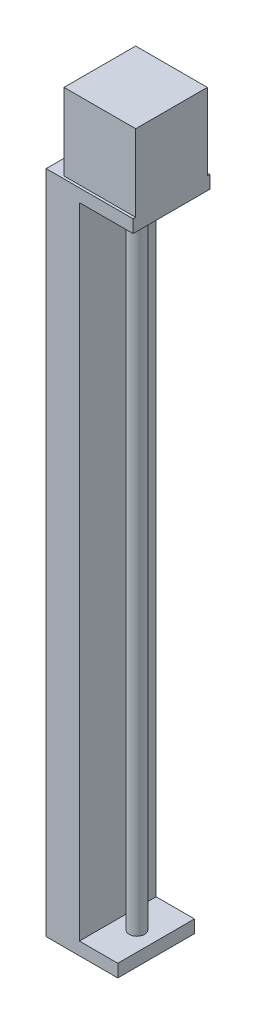
SolidWorks part; units mm, degrees
ref_plane "Front Plane" through (0, 0, 0) normal (0, 0, 1) x (1, 0, 0)
ref_plane "Top Plane" through (0, 0, 0) normal (0, 1, 0) x (1, 0, 0)
ref_plane "Right Plane" through (0, 0, 0) normal (1, 0, 0) x (0, 0, -1)
sketch "Sketch1" plane through (0, 0, 0) normal (0, 0, 1) x (1, 0, 0)
  line L0 (-11, 160) -> (-11, 130)
  line L1 (17, -125) -> (-17, -125)
  line L2 (17, -125) -> (17, 125)
  line L3 (17, 125) -> (-17, 125)
  line L4 (-17, -125) -> (-17, 125)
  line L5 (17, -125) -> (-17, 125) construction
  line L6 (17, 125) -> (-17, -125) construction
  line L7 (-17, -125) -> (11, -125)
  line L8 (-17, -125) -> (-17, -130)
  line L9 (-17, -130) -> (11, -130)
  line L10 (11, -125) -> (11, -130)
  line L11 (-17, 125) -> (17, 125)
  line L12 (-17, 125) -> (-17, 130)
  line L13 (-17, 130) -> (17, 130)
  line L14 (17, 125) -> (17, 130)
  line L15 (-17, 130) -> (17, 130)
  line L17 (-11, 160) -> (17, 160)
  line L18 (17, 130) -> (17, 160)
  line L19 (-4, 125) -> (-4, -125)
  point P0 (0, 0)
  dimension "D1" = 250
  dimension "D2" = 5
  dimension "D3" = 5
  dimension "D4" = 30
  dimension "D5" = 28
  dimension "D6" = 34
  dimension "D7" = 13
  dimension "D8" = 28
extrude "Boss-Extrude1" add sketch "Sketch1" along normal mid plane 30 contours L3 L14 L13 L12 L11 | L19 L11 L4 L7 | L10 L1 L7 L8 L9 region at (0, 127.5, 0) region at (-10.5, 0, 0) region at (-3, -127.5, 0)
extrude "Boss-Extrude2" add sketch "Sketch1<3>" along normal mid plane 28 contours L13 L18 L17 L0 region at (3, 145, 0)
sketch "Sketch1<3>" plane through (0, 0, 0) normal (0, 0, 1) x (1, 0, 0) same geometry as "Sketch1"
sketch "Sketch2" plane through (0, -125, 0) normal (0, 1, 0) x (1, 0, 0)
  line L0 (-4, 0) -> (11, 0) construction
  line L1 (-4, -15) -> (-4, 15) construction
  line L2 (11, -15) -> (11, 15) construction
  circle A0 centre (3.5, 0) radius 3
  point P9 (3.5, 0)
  dimension "D1" = 6
extrude "Boss-Extrude3" add sketch "Sketch2" along normal up to surface (250 mm away) up to face at (6.5, 125, 0)
